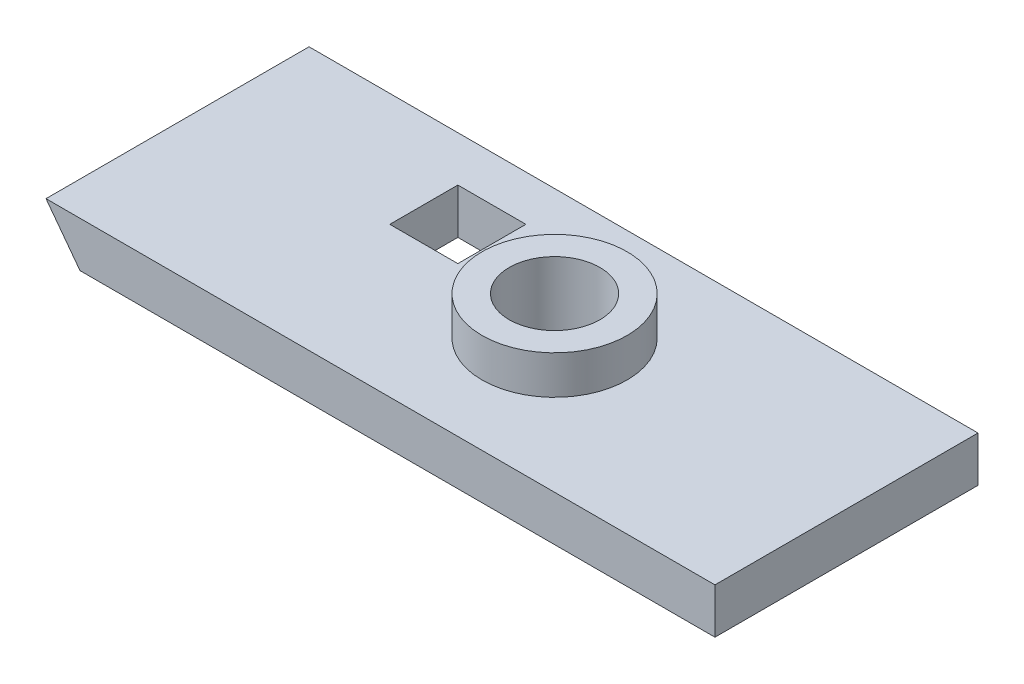
SolidWorks part; units mm, degrees
ref_plane "前视基准面" through (0, 0, 0) normal (0, 0, 1) x (1, 0, 0)
ref_plane "上视基准面" through (0, 0, 0) normal (0, 1, 0) x (1, 0, 0)
ref_plane "右视基准面" through (0, 0, 0) normal (1, 0, 0) x (0, 0, -1)
sketch "草图2" plane through (0, 0, 0) normal (0, 1, 0) x (1, 0, 0)
  line L1 (-30.1985, 7.2699) -> (-0.1985, 7.2699)
  line L2 (-30.1985, 7.2699) -> (-30.1985, -4.3301)
  line L3 (-30.1985, -4.3301) -> (-0.1985, -4.3301)
  line L4 (-0.1985, 7.2699) -> (-0.1985, -4.3301)
  line L5 (-32.1582, -4.3301) -> (-32.1582, 7.2699) construction
  line L7 (-0.1985, 1.4699) -> (-30.1985, 1.4699) construction
  line L9 (-34.0753, 7.2699) -> (0.3265, 7.2699) construction
  circle A1 centre (-15.1582, 1.5574) radius 2
  circle A2 centre (-15.1582, 1.5574) radius 3.2 construction
  circle A3 centre (-15.1582, 1.5574) radius 3.2 construction
  dimension "D4" = 4
  dimension "D5" = 6.4
  dimension "D1" = 30
extrude "凸台-拉伸1" add sketch "草图2" along normal blind 2
sketch "草图3" plane through (0, 2, 0) normal (0, 1, 0) x (1, 0, 0)
  circle A0 centre (-15.1582, 1.5574) radius 2
  circle A1 centre (-15.1582, 1.5574) radius 3.2
extrude "凸台-拉伸2" add sketch "草图3" along normal blind 1.7
sketch "草图4" plane through (0, 0, 0) normal (0, -1, 0) x (1, 0, 0)
  line L5 (-31.6367, 4.3301) -> (-31.6367, -7.2699) construction
  line L7 (-23.1367, -2.2699) -> (-20.1367, -2.2699)
  line L8 (-23.1367, -2.2699) -> (-23.1367, -5.2699)
  line L9 (-23.1367, -5.2699) -> (-20.1367, -5.2699)
  line L10 (-20.1367, -2.2699) -> (-20.1367, -5.2699)
  line L11 (-0.1985, -7.2699) -> (-30.1985, -7.2699) construction
  dimension "D1" = 3
  dimension "D3" = 5
  dimension "D2" = 8.5
extrude "切除-拉伸1" cut sketch "草图4" against normal blind 5
sketch "草图5" plane through (0, 0, -7.2699) normal (0, 0, -1) x (-1, 0, 0)
  line L0 (30.1985, 2) -> (30.1985, 0)
  line L1 (30.1985, 0) -> (31.6985, 2)
  line L2 (31.6985, 2) -> (30.1985, 2)
  line L6 (0.1985, 2) -> (30.1985, 2) construction
  line L7 (30.1985, 2) -> (30.1985, 0) construction
  dimension "D1" = 1.5
extrude "凸台-拉伸3" add sketch "草图5" against normal up to surface (11.6 mm away) up to face at (-15.1985, 1, 4.3301)
sketch "草图6" plane through (0, 0, 0) normal (0, -1, 0) x (1, 0, 0)
  line L0 (-0.1985, -7.2699) -> (-30.1985, -7.2699) construction
  line L1 (-0.1985, 4.3301) -> (-2.1985, 4.3301)
  line L2 (-0.1985, 4.3301) -> (-0.1985, -7.2699)
  line L3 (-0.1985, -7.2699) -> (-2.1985, -7.2699)
  line L4 (-2.1985, 4.3301) -> (-2.1985, -7.2699)
  dimension "D1" = 2
extrude "切除-拉伸2" cut sketch "草图6" against normal through all
sketch "草图7" plane through (0, 0, -7.2699) normal (0, 0, -1) x (-1, 0, 0)
  line L0 (31.6985, 2) -> (30.1985, 0)
  line L1 (30.1985, 0) -> (29.586, 0)
  line L2 (2.1985, 0) -> (30.1985, 0) construction
  line L3 (29.586, 0) -> (31.086, 2)
  line L4 (2.1985, 2) -> (31.6985, 2) construction
  line L5 (31.086, 2) -> (31.6985, 2)
  dimension "D1" = 0.49
